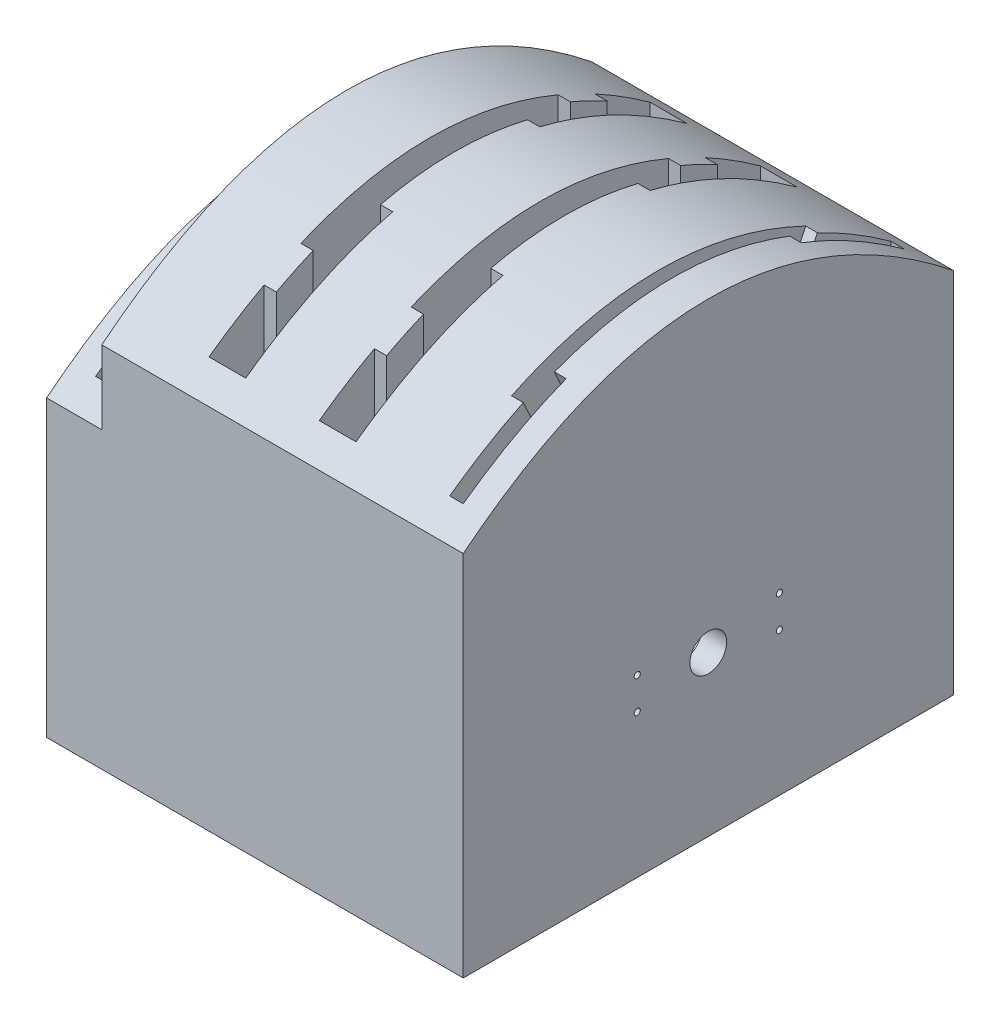
SolidWorks part; units mm, degrees
ref_plane "Front Plane" through (0, 0, 0) normal (0, 0, 1) x (1, 0, 0)
ref_plane "Top Plane" through (0, 0, 0) normal (0, 1, 0) x (1, 0, 0)
ref_plane "Right Plane" through (0, 0, 0) normal (1, 0, 0) x (0, 0, -1)
sketch "Sketch1" plane through (0, 0, 0) normal (1, 0, 0) x (0, 0, -1)
  line L2 (-100, 85) -> (-100, -65)
  line L3 (-100, -65) -> (100, -65)
  line L4 (100, 85) -> (100, -65)
  spline S0 degree 2 poles (-100, 85) (0, 165) (100, 85) knots 0 0 0 1 1 1
  point P4 (-100, 85)
  point P5 (100, 85)
  dimension "D1" = 200
  dimension "D2" = 100
  dimension "D3" = 150
  dimension "D4" = 150
  dimension "D5" = 40
  dimension "D6" = 100
  dimension "D7" = 125
extrude "Base" add sketch "Sketch1" along normal blind 170
ref_plane "New Top" through (0, 125, 0) normal (0, 1, 0) x (1, 0, 0)
sketch "Sketch3" plane through (0, 125, 0) normal (0, 1, 0) x (1, 0, 0)
  line L0 (170, -100) -> (170, 100) construction
  line L1 (116.25, 90) -> (101.25, 90)
  line L2 (116.25, 90) -> (116.25, 30)
  line L3 (116.25, -90) -> (101.25, -90)
  line L4 (101.25, 90) -> (101.25, 67.5)
  line L5 (86.25, -104.5688) -> (86.25, 145.9081) construction
  line L6 (101.25, 52.5) -> (106.25, 52.5)
  line L7 (170, 100) -> (0, 100) construction
  line L12 (170, -100) -> (0, -100) construction
  line L14 (101.25, 67.5) -> (106.25, 67.5)
  line L15 (106.25, 52.5) -> (106.25, 67.5)
  line L16 (116.25, 30) -> (111.25, 30)
  line L18 (116.25, -30) -> (111.25, -30)
  line L19 (111.25, 30) -> (111.25, -30)
  line L20 (101.25, -67.5) -> (106.25, -67.5)
  line L22 (101.25, -52.5) -> (106.25, -52.5)
  line L23 (106.25, -67.5) -> (106.25, -52.5)
  line L24 (71.25, 90) -> (56.25, 90)
  line L25 (71.25, 90) -> (71.25, 30)
  line L26 (71.25, -90) -> (56.25, -90)
  line L27 (56.25, 90) -> (56.25, 67.5)
  line L28 (56.25, 52.5) -> (61.25, 52.5)
  line L30 (56.25, 67.5) -> (61.25, 67.5)
  line L31 (61.25, 52.5) -> (61.25, 67.5)
  line L32 (71.25, 30) -> (66.25, 30)
  line L34 (71.25, -30) -> (66.25, -30)
  line L35 (66.25, 30) -> (66.25, -30)
  line L36 (56.25, -67.5) -> (61.25, -67.5)
  line L38 (56.25, -52.5) -> (61.25, -52.5)
  line L39 (61.25, -67.5) -> (61.25, -52.5)
  line L40 (116.25, -30) -> (116.25, -90)
  line L41 (71.25, -30) -> (71.25, -90)
  line L42 (56.25, 52.5) -> (56.25, -52.5)
  line L45 (56.25, -67.5) -> (56.25, -90)
  line L46 (101.25, -67.5) -> (101.25, -90)
  line L47 (101.25, 52.5) -> (101.25, -52.5)
  dimension "D1" = 53.75
  dimension "D2" = 15
  dimension "D3" = 15
  dimension "D4" = 2
  dimension "D5" = 15
  dimension "10" = 10
  dimension "D8" = 10
  dimension "D9" = 22.5
  dimension "D10" = 15
  dimension "D11" = 5
  dimension "D12" = 5
  dimension "D13" = 22.5
  dimension "D14" = 22.5
  dimension "D15" = 22.5
  dimension "D16" = 15
  dimension "D17" = 5
sketch "Sketch4" plane through (0, 125, 0) normal (0, 1, 0) x (1, 0, 0)
  line L1 (22.5, 87.5) -> (10, 87.5)
  line L2 (22.5, 87.5) -> (22.5, -87.5)
  line L3 (22.5, -87.5) -> (10, -87.5)
  line L4 (10, 87.5) -> (10, -87.5)
  line L5 (170, 100) -> (0, 100) construction
  line L6 (170, -100) -> (0, -100) construction
  line L7 (0, 100) -> (0, -100) construction
  dimension "D1" = 10
  dimension "D2" = 12.5
  dimension "D3" = 12.5
  dimension "D4" = 12.5
sketch "Sketch5" plane through (0, 125, 0) normal (0, 1, 0) x (1, 0, 0)
  line L0 (170, -100) -> (170, 100) construction
  line L1 (160, 90) -> (154.5, 90)
  line L2 (160, 90) -> (160, 48)
  line L3 (160, -90) -> (154.5, -90)
  line L4 (149.75, 60) -> (149.75, -60)
  line L5 (170, 100) -> (0, 100) construction
  line L6 (170, -100) -> (0, -100) construction
  line L7 (160, -48) -> (160, -90)
  line L10 (149.75, 60) -> (154.5, 60)
  line L11 (154.5, 90) -> (154.5, 60)
  line L12 (160, 48) -> (155.25, 48)
  line L14 (160, -48) -> (155.25, -48)
  line L15 (155.25, 48) -> (155.25, -48)
  line L18 (149.75, -60) -> (154.5, -60)
  line L19 (154.5, -90) -> (154.5, -60)
  dimension "D1" = 5.5
  dimension "D3" = 10
  dimension "D4" = 10
  dimension "D5" = 10
  dimension "D6" = 30
  dimension "D7" = 30
  dimension "D8" = 5.5
  dimension "D9" = 12
  dimension "D10" = 12
  dimension "D11" = 5.5
extrude "Flaps Cut" cut sketch "Sketch5" against normal up to surface (190 mm away) up to face at (85, -65, 0)
extrude "Throttle Cut" cut sketch "Sketch3" against normal up to surface (190 mm away) up to face at (155.6667, -65, 0)
extrude "Wing Sweep Cut" cut sketch "Sketch4" against normal up to surface (190 mm away) up to face at (107.5, -65, 0)
sketch "Sketch7" plane through (0, -65, 0) normal (0, -1, 0) x (1, 0, 0)
  line L0 (170, 100) -> (0, 100) construction
  line L1 (10, 90) -> (160, 90)
  line L2 (10, 90) -> (10, -90)
  line L3 (10, -90) -> (160, -90)
  line L4 (160, 90) -> (160, -90)
  dimension "D1" = 10
extrude "Bottom Cut" cut sketch "Sketch7" against normal blind 140
sketch "Sketch6" plane through (0, 0, 0) normal (-1, 0, 0) x (0, 0, 1)
  circle A0 centre (0, 0) radius 7.5
  dimension "D1" = 15
  dimension "D2" = 0
extrude "Cut-Extrude1" cut sketch "Sketch6" against normal up to next from surface starting at face at (160, 54.596, -5.25)
sketch "Sketch8" plane through (170, 0, 0) normal (1, 0, 0) x (0, 0, -1)
  line L0 (-52.1418, 0) -> (41.3037, 0) construction
  circle A0 centre (-29, 6.5) radius 1.25
  circle A1 centre (29, 6.5) radius 1.25
  circle A2 centre (29, -6.5) radius 1.25
  circle A3 centre (-29, -6.5) radius 1.25
  dimension "D2" = 2.5
  dimension "D4" = 2.5
  dimension "D1" = 29
  dimension "D3" = 6.5
  dimension "D5" = 29
  dimension "D6" = 6.5
extrude "Cut-Extrude3" cut sketch "Sketch8" against normal blind 10
sketch "Sketch20" plane through (155.25, 0, 0) normal (-1, 0, 0) x (0, 0, 1)
  line L0 (48, 115.784) -> (25.5, 65.784)
  line L1 (25.5, 65.784) -> (48, 65.784)
  line L2 (48, 65.784) -> (48, 115.784)
  line L3 (-48, 115.784) -> (-48, 65.784)
  line L4 (-48, 65.784) -> (-24.5, 65.784)
  line L5 (-24.5, 65.784) -> (-48, 115.784)
  dimension "D1" = 90
  dimension "D2" = 22.5
  dimension "D3" = 50
  dimension "D4" = 50
  dimension "D5" = 23.5
extrude "Cut-Extrude10" cut sketch "Sketch20" against normal blind 4.75
sketch "Sketch22" plane through (160, 0, 0) normal (-1, 0, 0) x (0, 0, 1)
  line L0 (-60, 110.6) -> (-43, 75)
  line L2 (-43, 75) -> (-60, 75)
  line L3 (-60, 75) -> (-60, 110.6)
  line L4 (-60, 75) -> (-60, 110.6) construction
  line L5 (60, 110.6) -> (60, 75)
  line L11 (60, 75) -> (43.75, 75)
  line L12 (43.75, 75) -> (60, 110.6)
  line L13 (-90, 75) -> (-60, 75) construction
  line L14 (60, 75) -> (90, 75) construction
  dimension "D1" = 0
  dimension "D2" = 17
  dimension "D3" = 90
  dimension "D4" = 0
  dimension "D5" = 16.25
  dimension "D6" = 0
  dimension "D7" = 0
  dimension "D8" = 0
extrude "Boss-Extrude5" add sketch "Sketch22" against normal blind 4.75 from surface starting at face at (149.75, 92.8, 15)
sketch "Sketch9" plane through (0, 0, 0) normal (-1, 0, 0) x (0, 0, 1)
  line L0 (100, 85) -> (100, -65) construction
  line L1 (-100, 55) -> (-100, 135)
  line L2 (-100, 135) -> (100, 135)
  line L3 (100, 135) -> (100, 55)
  spline S0 degree 2 poles (-100, 55) (0, 135) (100, 55) knots 0 0 0 1 1 1
  dimension "D1" = 100
  dimension "D2" = 40
  dimension "D3" = 100
  dimension "D4" = 40
  dimension "D5" = 0
  dimension "D6" = 30
  dimension "D7" = 80
extrude "Cut-Extrude4" cut sketch "Sketch9" against normal up to surface (22.5 mm away) up to face at (22.5, 84.6875, -21.875)
sketch "Sketch13" plane through (0, 75, 0) normal (0, -1, 0) x (1, 0, 0)
  line L0 (56.25, 90) -> (22.5, 90) construction
  line L1 (22.5, 90) -> (32.5, 90)
  line L2 (22.5, 90) -> (22.5, -90)
  line L3 (22.5, -90) -> (32.5, -90)
  line L4 (32.5, 90) -> (32.5, -90)
  line L5 (22.5, -90) -> (56.25, -90) construction
  point P5 (0, 0)
  dimension "D1" = 10
  dimension "D2" = 0
  dimension "D3" = 0
extrude "Boss-Extrude2" add sketch "Sketch13" along normal blind 140
sketch "Sketch12" plane through (22.5, 0, 0) normal (-1, 0, 0) x (0, 0, 1)
  line L0 (-48.4309, 58.2758) -> (-48.4309, 55.2758)
  line L1 (100, 27.75) -> (100, 24.75)
  spline S0 degree 3 poles (-48.4309, 58.2758) (3.558, 77.5898) (53.0349, 67.4145) (100, 27.75) knots 0.031016 0.031016 0.031016 0.031016 1 1 1 1
  spline S1 degree 3 poles (100, 24.75) (53.0349, 64.4145) (3.558, 74.5898) (-48.4309, 55.2758) knots 0 0 0 0 0.968984 0.968984 0.968984 0.968984
  point P0 (0, 64.75)
  point P2 (100, 24.75)
  point P4 (0, 67.75)
  point P5 (-100, 23.75)
  point P6 (100, 27.75)
  dimension "D1" = 100
  dimension "D4" = 40
  dimension "D5" = 40
  dimension "D6" = 100
  dimension "D8" = 27.25
  dimension "D9" = 3
extrude "Boss-Extrude1" add sketch "Sketch12" along normal blind 2.5
sketch "Sketch10" plane through (10, 0, 0) normal (1, 0, 0) x (0, 0, -1)
  circle A5 centre (0, -30) radius 7.5
  dimension "D1" = 15
  dimension "D6" = 30
extrude "Cut-Extrude5" cut sketch "Sketch10" along normal blind 10 from surface starting at face at (22.5, 38.0995, -2.2385)
sketch "Sketch14" plane through (22.5, 0, 0) normal (-1, 0, 0) x (0, 0, 1)
  circle A0 centre (47.4611, -24.9378) radius 5
extrude "Cut-Extrude6" cut sketch "Sketch14" against normal blind 10
sketch "Sketch16" plane through (22.5, 0, 0) normal (-1, 0, 0) x (0, 0, 1)
  line L0 (-67.9611, -27.5) -> (138.1953, -27.5) construction
  circle A0 centre (80, -55) radius 1.25
  circle A1 centre (15, -55) radius 1.25
  circle A4 centre (15, 0) radius 1.25
  circle A5 centre (80, 0) radius 1.25
  dimension "D5" = 2.5
  dimension "D6" = 2.5
  dimension "D7" = 27.5
  dimension "D1" = 55
  dimension "D2" = 80
  dimension "D3" = 15
  dimension "D4" = 55
extrude "Cut-Extrude9" cut sketch "Sketch16" against normal blind 10
sketch "Sketch17" plane through (22.5, 0, 0) normal (-1, 0, 0) x (0, 0, 1)
  line L0 (-49.7797, 57.8455) -> (-56.5642, 70.771)
  line L1 (-56.5642, 70.771) -> (-59.2205, 69.3767)
  line L2 (-59.2205, 69.3767) -> (-51.0872, 53.8816)
  line L3 (-51.0872, 53.8816) -> (-48.4309, 55.2758)
  line L5 (-48.4309, 58.2758) -> (-49.7797, 57.8455)
  line L6 (-48.4309, 58.2758) -> (-48.4309, 55.2758)
  dimension "D1" = 90
  dimension "25" = 17.5
  dimension "D2" = 3
  dimension "D3" = 90
  dimension "D4" = 90
  dimension "D5" = 100
extrude "Boss-Extrude3" add sketch "Sketch17" along normal blind 2.5
sketch "Sketch19" plane through (22.5, 0, 0) normal (-1, 0, 0) x (0, 0, 1)
  line L0 (-100, -65) -> (-100, 55) construction
  line L1 (-55.7563, 69.232) -> (-56.9133, 71.6936)
  line L2 (-49.7797, 57.8455) -> (-56.5642, 70.771) construction
  line L3 (-100, 45.5) -> (-100, 42.5)
  spline S0 degree 2 poles (-100, 42.5) (-76.9596, 59.4626) (-55.7563, 69.232) knots 0 0 0 0.212033 0.212033 0.212033
  spline S1 degree 2 poles (-100, 45.5) (-77.5381, 61.9998) (-56.9133, 71.6936) knots 0 0 0 0.206248 0.206248 0.206248
  dimension "D6" = 12.5
  dimension "D4" = 26.732
  dimension "D3" = 2.7199
  dimension "D5" = 0
  dimension "D11" = 0
  dimension "D12" = 3
extrude "Boss-Extrude4" add sketch "Sketch19" along normal blind 2.5
fillet "Fillet1" radius 2.5 4 edges at (21.25, 53.8816, -51.0872) (21.25, 57.8455, -49.7797) (21.25, 67.954, -58.4737) (21.25, 71.6936, -56.9133)
